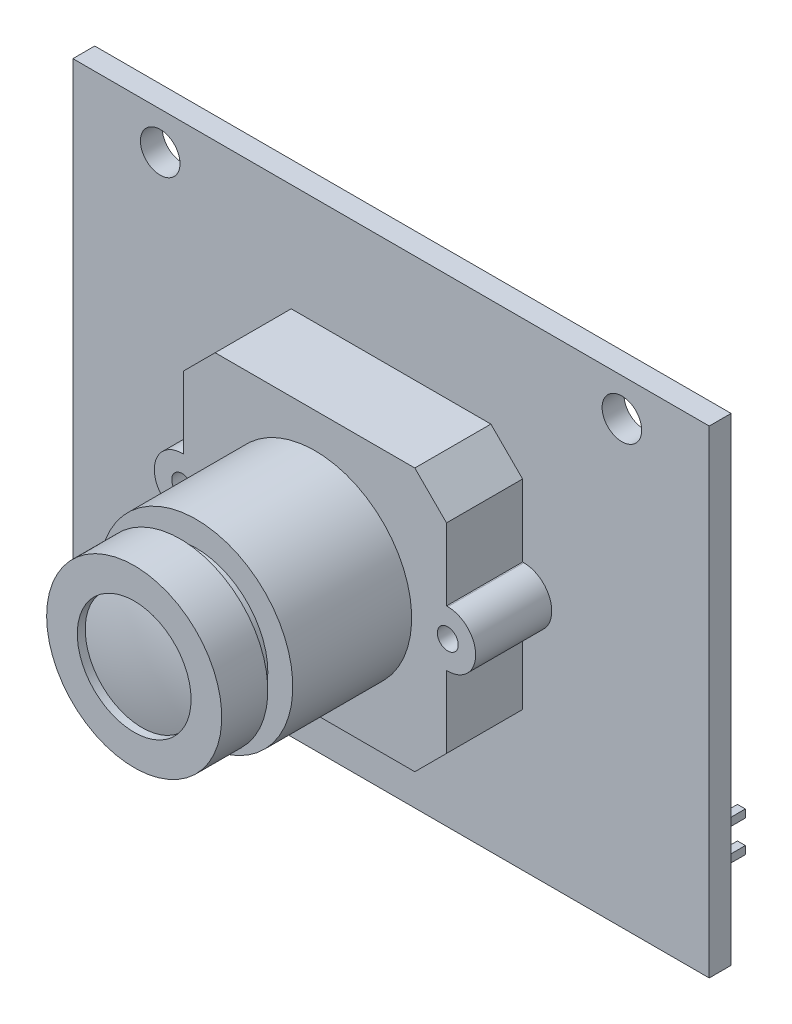
SolidWorks part; units mm, degrees
ref_plane "Front Plane" through (0, 0, 0) normal (0, 0, 1) x (1, 0, 0)
ref_plane "Top Plane" through (0, 0, 0) normal (0, 1, 0) x (1, 0, 0)
ref_plane "Right Plane" through (0, 0, 0) normal (1, 0, 0) x (0, 0, -1)
sketch "Sketch1" plane through (0, 0, 0) normal (0, 0, 1) x (1, 0, 0)
  line L1 (0, 38.31) -> (51, 38.31)
  line L2 (0, 38.31) -> (0, 0)
  line L3 (0, 0) -> (51, 0)
  line L4 (51, 38.31) -> (51, 0)
  dimension "D1" = 38.31
  dimension "D2" = 51
extrude "Boss-Extrude1" add sketch "Sketch1" along normal blind 1.7526
sketch "Sketch2" plane through (0, 0, 1.7526) normal (0, 0, 1) x (1, 0, 0)
  line L0 (7, 35.31) -> (44, 35.31) construction
  line L1 (25.5, 38.31) -> (25.5, 35.31) construction
  line L2 (51, 38.31) -> (0, 38.31) construction
  circle A0 centre (44, 35.31) radius 1.5875
  circle A1 centre (7, 35.31) radius 1.5875
  dimension "D2" = 3.175
  dimension "D3" = 3
  dimension "D1" = 37
extrude "Cut-Extrude1" cut sketch "Sketch2" against normal up to surface (1.7526 mm away) up to face at (25.5, 19.155, 0)
sketch "Sketch3" plane through (0, 0, 1.7526) normal (0, 0, 1) x (1, 0, 0)
  line L0 (25.5, 38.31) -> (25.5, 0) construction
  line L1 (51, 38.31) -> (0, 38.31) construction
  line L2 (0, 0) -> (51, 0) construction
  line L3 (14.959, 19.155) -> (36.041, 19.155) construction
  line L4 (14.959, 29.696) -> (36.041, 29.696)
  line L5 (14.959, 29.696) -> (14.959, 8.614)
  line L6 (14.959, 8.614) -> (36.041, 8.614)
  line L7 (36.041, 29.696) -> (36.041, 8.614)
  point P12 (25.5, 19.155)
  dimension "D1" = 21.082
extrude "Boss-Extrude2" add sketch "Sketch3" along normal blind 6.096
chamfer "Chamfer1" distance 2.54 angle 45 4 edges at (36.041, 8.614, 4.8006) (14.959, 8.614, 4.8006) (14.959, 29.696, 4.8006) (36.041, 29.696, 4.8006)
sketch "Sketch5" plane through (0, 0, 1.7526) normal (0, 0, 1) x (1, 0, 0)
  line L0 (36.041, 29.696) -> (36.041, 8.614) construction
  line L1 (36.041, 21.3902) -> (36.1426, 21.3902)
  line L3 (36.041, 21.3902) -> (36.041, 16.9198)
  line L4 (36.041, 16.9198) -> (36.1426, 16.9198)
  line L5 (36.1426, 21.3902) -> (36.1426, 16.9198) construction
  line L6 (14.959, 29.696) -> (14.959, 8.614) construction
  line L7 (14.8574, 21.3902) -> (14.959, 21.3902)
  line L8 (14.8574, 21.3902) -> (14.8574, 16.9198) construction
  line L9 (14.8574, 16.9198) -> (14.959, 16.9198)
  line L10 (14.959, 21.3902) -> (14.959, 16.9198)
  arc A0 (36.1426, 21.3902) -> (36.1426, 16.9198) centre (36.1426, 19.155) cw
  arc A1 (14.8574, 21.3902) -> (14.8574, 16.9198) centre (14.8574, 19.155) ccw
  dimension "D1" = 4.4704
  dimension "D3" = 21.2852
extrude "Boss-Extrude4" add sketch "Sketch5" along normal up to surface (6.096 mm away) up to face at (25.5, 19.155, 7.8486)
sketch "Sketch7" plane through (0, 0, 7.8486) normal (0, 0, 1) x (1, 0, 0)
  circle A0 centre (14.8574, 19.155) radius 0.8382
  circle A1 centre (36.1426, 19.155) radius 0.8382
  dimension "D1" = 1.6764
extrude "Cut-Extrude2" cut sketch "Sketch7" against normal up to surface (7.8486 mm away) up to face at (45.5875, 35.31, 0)
sketch "Sketch4" plane through (0, 0, 7.8486) normal (0, 0, 1) x (1, 0, 0)
  circle A0 centre (25.5, 19.155) radius 7.747
  dimension "D1" = 15.494
extrude "Boss-Extrude3" add sketch "Sketch4" along normal blind 9.525
sketch "Sketch8" plane through (0, 0, 17.3736) normal (0, 0, 1) x (1, 0, 0)
  circle A0 centre (25.5, 19.155) radius 5.7468
  circle A1 centre (25.5, 19.155) radius 7.747 construction
  dimension "D1" = 11.4935
extrude "Boss-Extrude5" add sketch "Sketch8" along normal blind 1.27
sketch "Sketch9" plane through (0, 0, 18.6436) normal (0, 0, 1) x (1, 0, 0)
  circle A0 centre (25.5, 19.155) radius 7.0167
  circle A1 centre (25.5, 19.155) radius 5.7468 construction
  dimension "D1" = 14.0335
extrude "Boss-Extrude6" add sketch "Sketch9" along normal blind 3.6957
sketch "Sketch10" plane through (0, 0, 22.3393) normal (0, 0, 1) x (1, 0, 0)
  circle A0 centre (25.5, 19.155) radius 4.5599
  circle A1 centre (25.5, 19.155) radius 7.0167 construction
extrude "Cut-Extrude3" cut sketch "Sketch10" against normal blind 0.635
dome "Dome1" faces to dome 1 distance 0.508 reverse direction no elliptical dome no face at (30.0599, 19.155, 21.7043) parameters "D1"=0.508
sketch "Sketch12" plane through (0, 0, 0) normal (0, 0, -1) x (-1, 0, 0)
  line L0 (0, 0) -> (-51, 0) construction
  line L1 (-45.92, 2.667) -> (-43.507, 2.667)
  line L2 (-45.92, 2.667) -> (-45.92, 0.254)
  line L3 (-45.92, 0.254) -> (-43.507, 0.254)
  line L4 (-43.507, 2.667) -> (-43.507, 0.254)
  line L5 (-51, 0) -> (-51, 38.31) construction
  line L6 (-43.38, 2.667) -> (-40.967, 2.667)
  line L7 (-43.38, 2.667) -> (-43.38, 0.254)
  line L8 (-43.38, 0.254) -> (-40.967, 0.254)
  line L9 (-40.967, 2.667) -> (-40.967, 0.254)
  line L10 (-40.84, 2.667) -> (-38.427, 2.667)
  line L11 (-40.84, 2.667) -> (-40.84, 0.254)
  line L12 (-40.84, 0.254) -> (-38.427, 0.254)
  line L13 (-38.427, 2.667) -> (-38.427, 0.254)
  line L14 (-38.3, 2.667) -> (-35.887, 2.667)
  line L15 (-38.3, 2.667) -> (-38.3, 0.254)
  line L16 (-38.3, 0.254) -> (-35.887, 0.254)
  line L17 (-35.887, 2.667) -> (-35.887, 0.254)
  line L18 (-35.76, 2.667) -> (-33.347, 2.667)
  line L19 (-35.76, 2.667) -> (-35.76, 0.254)
  line L20 (-35.76, 0.254) -> (-33.347, 0.254)
  line L21 (-33.347, 2.667) -> (-33.347, 0.254)
  line L22 (-33.22, 2.667) -> (-30.807, 2.667)
  line L23 (-33.22, 2.667) -> (-33.22, 0.254)
  line L24 (-33.22, 0.254) -> (-30.807, 0.254)
  line L25 (-30.807, 2.667) -> (-30.807, 0.254)
  line L26 (-30.68, 2.667) -> (-28.267, 2.667)
  line L27 (-30.68, 2.667) -> (-30.68, 0.254)
  line L28 (-30.68, 0.254) -> (-28.267, 0.254)
  line L29 (-28.267, 2.667) -> (-28.267, 0.254)
  line L30 (-28.14, 2.667) -> (-25.727, 2.667)
  line L31 (-28.14, 2.667) -> (-28.14, 0.254)
  line L32 (-28.14, 0.254) -> (-25.727, 0.254)
  line L33 (-25.727, 2.667) -> (-25.727, 0.254)
  line L34 (-25.6, 2.667) -> (-23.187, 2.667)
  line L35 (-25.6, 2.667) -> (-25.6, 0.254)
  line L36 (-25.6, 0.254) -> (-23.187, 0.254)
  line L37 (-23.187, 2.667) -> (-23.187, 0.254)
  line L38 (-23.06, 2.667) -> (-20.647, 2.667)
  line L39 (-23.06, 2.667) -> (-23.06, 0.254)
  line L40 (-23.06, 0.254) -> (-20.647, 0.254)
  line L41 (-20.647, 2.667) -> (-20.647, 0.254)
  line L42 (-20.52, 2.667) -> (-18.107, 2.667)
  line L43 (-20.52, 2.667) -> (-20.52, 0.254)
  line L44 (-20.52, 0.254) -> (-18.107, 0.254)
  line L45 (-18.107, 2.667) -> (-18.107, 0.254)
  line L46 (-17.98, 2.667) -> (-15.567, 2.667)
  line L47 (-17.98, 2.667) -> (-17.98, 0.254)
  line L48 (-17.98, 0.254) -> (-15.567, 0.254)
  line L49 (-15.567, 2.667) -> (-15.567, 0.254)
  line L50 (-15.44, 2.667) -> (-13.027, 2.667)
  line L51 (-15.44, 2.667) -> (-15.44, 0.254)
  line L52 (-15.44, 0.254) -> (-13.027, 0.254)
  line L53 (-13.027, 2.667) -> (-13.027, 0.254)
  line L54 (-12.9, 2.667) -> (-10.487, 2.667)
  line L55 (-12.9, 2.667) -> (-12.9, 0.254)
  line L56 (-12.9, 0.254) -> (-10.487, 0.254)
  line L57 (-10.487, 2.667) -> (-10.487, 0.254)
  line L58 (-10.36, 2.667) -> (-7.947, 2.667)
  line L59 (-10.36, 2.667) -> (-10.36, 0.254)
  line L60 (-10.36, 0.254) -> (-7.947, 0.254)
  line L61 (-7.947, 2.667) -> (-7.947, 0.254)
  line L62 (-7.82, 2.667) -> (-5.407, 2.667)
  line L63 (-7.82, 2.667) -> (-7.82, 0.254)
  line L64 (-7.82, 0.254) -> (-5.407, 0.254)
  line L65 (-5.407, 2.667) -> (-5.407, 0.254)
  line L66 (-43.38, 5.207) -> (-40.967, 5.207)
  line L67 (-43.38, 5.207) -> (-43.38, 2.794)
  line L68 (-43.38, 2.794) -> (-40.967, 2.794)
  line L69 (-40.967, 5.207) -> (-40.967, 2.794)
  line L70 (-40.84, 5.207) -> (-38.427, 5.207)
  line L71 (-40.84, 5.207) -> (-40.84, 2.794)
  line L72 (-40.84, 2.794) -> (-38.427, 2.794)
  line L73 (-38.427, 5.207) -> (-38.427, 2.794)
  line L74 (-38.3, 5.207) -> (-35.887, 5.207)
  line L75 (-38.3, 5.207) -> (-38.3, 2.794)
  line L76 (-38.3, 2.794) -> (-35.887, 2.794)
  line L77 (-35.887, 5.207) -> (-35.887, 2.794)
  line L78 (-35.76, 5.207) -> (-33.347, 5.207)
  line L79 (-35.76, 5.207) -> (-35.76, 2.794)
  line L80 (-35.76, 2.794) -> (-33.347, 2.794)
  line L81 (-33.347, 5.207) -> (-33.347, 2.794)
  line L82 (-33.22, 5.207) -> (-30.807, 5.207)
  line L83 (-33.22, 5.207) -> (-33.22, 2.794)
  line L84 (-33.22, 2.794) -> (-30.807, 2.794)
  line L85 (-30.807, 5.207) -> (-30.807, 2.794)
  line L86 (-30.68, 5.207) -> (-28.267, 5.207)
  line L87 (-30.68, 5.207) -> (-30.68, 2.794)
  line L88 (-30.68, 2.794) -> (-28.267, 2.794)
  line L89 (-28.267, 5.207) -> (-28.267, 2.794)
  line L90 (-28.14, 5.207) -> (-25.727, 5.207)
  line L91 (-28.14, 5.207) -> (-28.14, 2.794)
  line L92 (-28.14, 2.794) -> (-25.727, 2.794)
  line L93 (-25.727, 5.207) -> (-25.727, 2.794)
  line L94 (-25.6, 5.207) -> (-23.187, 5.207)
  line L95 (-25.6, 5.207) -> (-25.6, 2.794)
  line L96 (-25.6, 2.794) -> (-23.187, 2.794)
  line L97 (-23.187, 5.207) -> (-23.187, 2.794)
  line L98 (-23.06, 5.207) -> (-20.647, 5.207)
  line L99 (-23.06, 5.207) -> (-23.06, 2.794)
  line L100 (-23.06, 2.794) -> (-20.647, 2.794)
  line L101 (-20.647, 5.207) -> (-20.647, 2.794)
  line L102 (-20.52, 5.207) -> (-18.107, 5.207)
  line L103 (-20.52, 5.207) -> (-20.52, 2.794)
  line L104 (-20.52, 2.794) -> (-18.107, 2.794)
  line L105 (-18.107, 5.207) -> (-18.107, 2.794)
  line L106 (-17.98, 5.207) -> (-15.567, 5.207)
  line L107 (-17.98, 5.207) -> (-17.98, 2.794)
  line L108 (-17.98, 2.794) -> (-15.567, 2.794)
  line L109 (-15.567, 5.207) -> (-15.567, 2.794)
  line L110 (-15.44, 5.207) -> (-13.027, 5.207)
  line L111 (-15.44, 5.207) -> (-15.44, 2.794)
  line L112 (-15.44, 2.794) -> (-13.027, 2.794)
  line L113 (-13.027, 5.207) -> (-13.027, 2.794)
  line L114 (-12.9, 5.207) -> (-10.487, 5.207)
  line L115 (-12.9, 5.207) -> (-12.9, 2.794)
  line L116 (-12.9, 2.794) -> (-10.487, 2.794)
  line L117 (-10.487, 5.207) -> (-10.487, 2.794)
  line L118 (-10.36, 5.207) -> (-7.947, 5.207)
  line L119 (-10.36, 5.207) -> (-10.36, 2.794)
  line L120 (-10.36, 2.794) -> (-7.947, 2.794)
  line L121 (-7.947, 5.207) -> (-7.947, 2.794)
  line L122 (-7.82, 5.207) -> (-5.407, 5.207)
  line L123 (-7.82, 5.207) -> (-7.82, 2.794)
  line L124 (-7.82, 2.794) -> (-5.407, 2.794)
  line L125 (-5.407, 5.207) -> (-5.407, 2.794)
  line L126 (-45.92, 5.207) -> (-43.507, 5.207)
  line L127 (-45.92, 5.207) -> (-45.92, 2.794)
  line L128 (-45.92, 2.794) -> (-43.507, 2.794)
  line L129 (-43.507, 5.207) -> (-43.507, 2.794)
  dimension "D1" = 2.413
  dimension "D2" = 0.254
  dimension "D3" = 5.08
  dimension "D4" = 16
  dimension "D5" = 2
extrude "Boss-Extrude8" add sketch "Sketch12" along normal blind 1.27
sketch "Sketch13" plane through (0, 0, -1.27) normal (0, 0, -1) x (-1, 0, 0)
  line L0 (-44.7135, 2.667) -> (-44.7135, 0.254) construction
  line L3 (-43.507, 2.667) -> (-45.92, 2.667) construction
  line L4 (-45.92, 0.254) -> (-43.507, 0.254) construction
  line L5 (-45.031, 1.4605) -> (-44.396, 1.4605) construction
  line L6 (-42.491, 1.778) -> (-41.856, 1.778)
  line L7 (-45.031, 1.778) -> (-44.396, 1.778)
  line L8 (-45.031, 1.778) -> (-45.031, 1.143)
  line L9 (-45.031, 1.143) -> (-44.396, 1.143)
  line L10 (-44.396, 1.778) -> (-44.396, 1.143)
  line L11 (-41.856, 1.778) -> (-41.856, 1.143)
  line L12 (-42.491, 1.143) -> (-41.856, 1.143)
  line L13 (-42.491, 1.778) -> (-42.491, 1.143)
  line L14 (-39.951, 1.778) -> (-39.316, 1.778)
  line L15 (-39.316, 1.778) -> (-39.316, 1.143)
  line L16 (-39.951, 1.143) -> (-39.316, 1.143)
  line L17 (-39.951, 1.778) -> (-39.951, 1.143)
  line L18 (-37.411, 1.778) -> (-36.776, 1.778)
  line L19 (-36.776, 1.778) -> (-36.776, 1.143)
  line L20 (-37.411, 1.143) -> (-36.776, 1.143)
  line L21 (-37.411, 1.778) -> (-37.411, 1.143)
  line L22 (-34.871, 1.778) -> (-34.236, 1.778)
  line L23 (-34.236, 1.778) -> (-34.236, 1.143)
  line L24 (-34.871, 1.143) -> (-34.236, 1.143)
  line L25 (-34.871, 1.778) -> (-34.871, 1.143)
  line L26 (-32.331, 1.778) -> (-31.696, 1.778)
  line L27 (-31.696, 1.778) -> (-31.696, 1.143)
  line L28 (-32.331, 1.143) -> (-31.696, 1.143)
  line L29 (-32.331, 1.778) -> (-32.331, 1.143)
  line L30 (-29.791, 1.778) -> (-29.156, 1.778)
  line L31 (-29.156, 1.778) -> (-29.156, 1.143)
  line L32 (-29.791, 1.143) -> (-29.156, 1.143)
  line L33 (-29.791, 1.778) -> (-29.791, 1.143)
  line L34 (-27.251, 1.778) -> (-26.616, 1.778)
  line L35 (-26.616, 1.778) -> (-26.616, 1.143)
  line L36 (-27.251, 1.143) -> (-26.616, 1.143)
  line L37 (-27.251, 1.778) -> (-27.251, 1.143)
  line L38 (-24.711, 1.778) -> (-24.076, 1.778)
  line L39 (-24.076, 1.778) -> (-24.076, 1.143)
  line L40 (-24.711, 1.143) -> (-24.076, 1.143)
  line L41 (-24.711, 1.778) -> (-24.711, 1.143)
  line L42 (-22.171, 1.778) -> (-21.536, 1.778)
  line L43 (-21.536, 1.778) -> (-21.536, 1.143)
  line L44 (-22.171, 1.143) -> (-21.536, 1.143)
  line L45 (-22.171, 1.778) -> (-22.171, 1.143)
  line L46 (-19.631, 1.778) -> (-18.996, 1.778)
  line L47 (-18.996, 1.778) -> (-18.996, 1.143)
  line L48 (-19.631, 1.143) -> (-18.996, 1.143)
  line L49 (-19.631, 1.778) -> (-19.631, 1.143)
  line L50 (-17.091, 1.778) -> (-16.456, 1.778)
  line L51 (-16.456, 1.778) -> (-16.456, 1.143)
  line L52 (-17.091, 1.143) -> (-16.456, 1.143)
  line L53 (-17.091, 1.778) -> (-17.091, 1.143)
  line L54 (-14.551, 1.778) -> (-13.916, 1.778)
  line L55 (-13.916, 1.778) -> (-13.916, 1.143)
  line L56 (-14.551, 1.143) -> (-13.916, 1.143)
  line L57 (-14.551, 1.778) -> (-14.551, 1.143)
  line L58 (-12.011, 1.778) -> (-11.376, 1.778)
  line L59 (-11.376, 1.778) -> (-11.376, 1.143)
  line L60 (-12.011, 1.143) -> (-11.376, 1.143)
  line L61 (-12.011, 1.778) -> (-12.011, 1.143)
  line L62 (-9.471, 1.778) -> (-8.836, 1.778)
  line L63 (-8.836, 1.778) -> (-8.836, 1.143)
  line L64 (-9.471, 1.143) -> (-8.836, 1.143)
  line L65 (-9.471, 1.778) -> (-9.471, 1.143)
  line L66 (-6.931, 1.778) -> (-6.296, 1.778)
  line L67 (-6.296, 1.778) -> (-6.296, 1.143)
  line L68 (-6.931, 1.143) -> (-6.296, 1.143)
  line L69 (-6.931, 1.778) -> (-6.931, 1.143)
  line L70 (-42.491, 4.318) -> (-41.856, 4.318)
  line L71 (-41.856, 4.318) -> (-41.856, 3.683)
  line L72 (-42.491, 3.683) -> (-41.856, 3.683)
  line L73 (-42.491, 4.318) -> (-42.491, 3.683)
  line L74 (-39.951, 4.318) -> (-39.316, 4.318)
  line L75 (-39.316, 4.318) -> (-39.316, 3.683)
  line L76 (-39.951, 3.683) -> (-39.316, 3.683)
  line L77 (-39.951, 4.318) -> (-39.951, 3.683)
  line L78 (-37.411, 4.318) -> (-36.776, 4.318)
  line L79 (-36.776, 4.318) -> (-36.776, 3.683)
  line L80 (-37.411, 3.683) -> (-36.776, 3.683)
  line L81 (-37.411, 4.318) -> (-37.411, 3.683)
  line L82 (-34.871, 4.318) -> (-34.236, 4.318)
  line L83 (-34.236, 4.318) -> (-34.236, 3.683)
  line L84 (-34.871, 3.683) -> (-34.236, 3.683)
  line L85 (-34.871, 4.318) -> (-34.871, 3.683)
  line L86 (-32.331, 4.318) -> (-31.696, 4.318)
  line L87 (-31.696, 4.318) -> (-31.696, 3.683)
  line L88 (-32.331, 3.683) -> (-31.696, 3.683)
  line L89 (-32.331, 4.318) -> (-32.331, 3.683)
  line L90 (-29.791, 4.318) -> (-29.156, 4.318)
  line L91 (-29.156, 4.318) -> (-29.156, 3.683)
  line L92 (-29.791, 3.683) -> (-29.156, 3.683)
  line L93 (-29.791, 4.318) -> (-29.791, 3.683)
  line L94 (-27.251, 4.318) -> (-26.616, 4.318)
  line L95 (-26.616, 4.318) -> (-26.616, 3.683)
  line L96 (-27.251, 3.683) -> (-26.616, 3.683)
  line L97 (-27.251, 4.318) -> (-27.251, 3.683)
  line L98 (-24.711, 4.318) -> (-24.076, 4.318)
  line L99 (-24.076, 4.318) -> (-24.076, 3.683)
  line L100 (-24.711, 3.683) -> (-24.076, 3.683)
  line L101 (-24.711, 4.318) -> (-24.711, 3.683)
  line L102 (-22.171, 4.318) -> (-21.536, 4.318)
  line L103 (-21.536, 4.318) -> (-21.536, 3.683)
  line L104 (-22.171, 3.683) -> (-21.536, 3.683)
  line L105 (-22.171, 4.318) -> (-22.171, 3.683)
  line L106 (-19.631, 4.318) -> (-18.996, 4.318)
  line L107 (-18.996, 4.318) -> (-18.996, 3.683)
  line L108 (-19.631, 3.683) -> (-18.996, 3.683)
  line L109 (-19.631, 4.318) -> (-19.631, 3.683)
  line L110 (-17.091, 4.318) -> (-16.456, 4.318)
  line L111 (-16.456, 4.318) -> (-16.456, 3.683)
  line L112 (-17.091, 3.683) -> (-16.456, 3.683)
  line L113 (-17.091, 4.318) -> (-17.091, 3.683)
  line L114 (-14.551, 4.318) -> (-13.916, 4.318)
  line L115 (-13.916, 4.318) -> (-13.916, 3.683)
  line L116 (-14.551, 3.683) -> (-13.916, 3.683)
  line L117 (-14.551, 4.318) -> (-14.551, 3.683)
  line L118 (-12.011, 4.318) -> (-11.376, 4.318)
  line L119 (-11.376, 4.318) -> (-11.376, 3.683)
  line L120 (-12.011, 3.683) -> (-11.376, 3.683)
  line L121 (-12.011, 4.318) -> (-12.011, 3.683)
  line L122 (-9.471, 4.318) -> (-8.836, 4.318)
  line L123 (-8.836, 4.318) -> (-8.836, 3.683)
  line L124 (-9.471, 3.683) -> (-8.836, 3.683)
  line L125 (-9.471, 4.318) -> (-9.471, 3.683)
  line L126 (-6.931, 4.318) -> (-6.296, 4.318)
  line L127 (-6.296, 4.318) -> (-6.296, 3.683)
  line L128 (-6.931, 3.683) -> (-6.296, 3.683)
  line L129 (-6.931, 4.318) -> (-6.931, 3.683)
  line L130 (-45.031, 4.318) -> (-44.396, 4.318)
  line L131 (-44.396, 4.318) -> (-44.396, 3.683)
  line L132 (-45.031, 3.683) -> (-44.396, 3.683)
  line L133 (-45.031, 4.318) -> (-45.031, 3.683)
  point P8 (-44.7135, 1.4605)
  dimension "D1" = 0.635
  dimension "D2" = 16
  dimension "D3" = 2
extrude "Boss-Extrude9" add sketch "Sketch13" along normal blind 5.842
